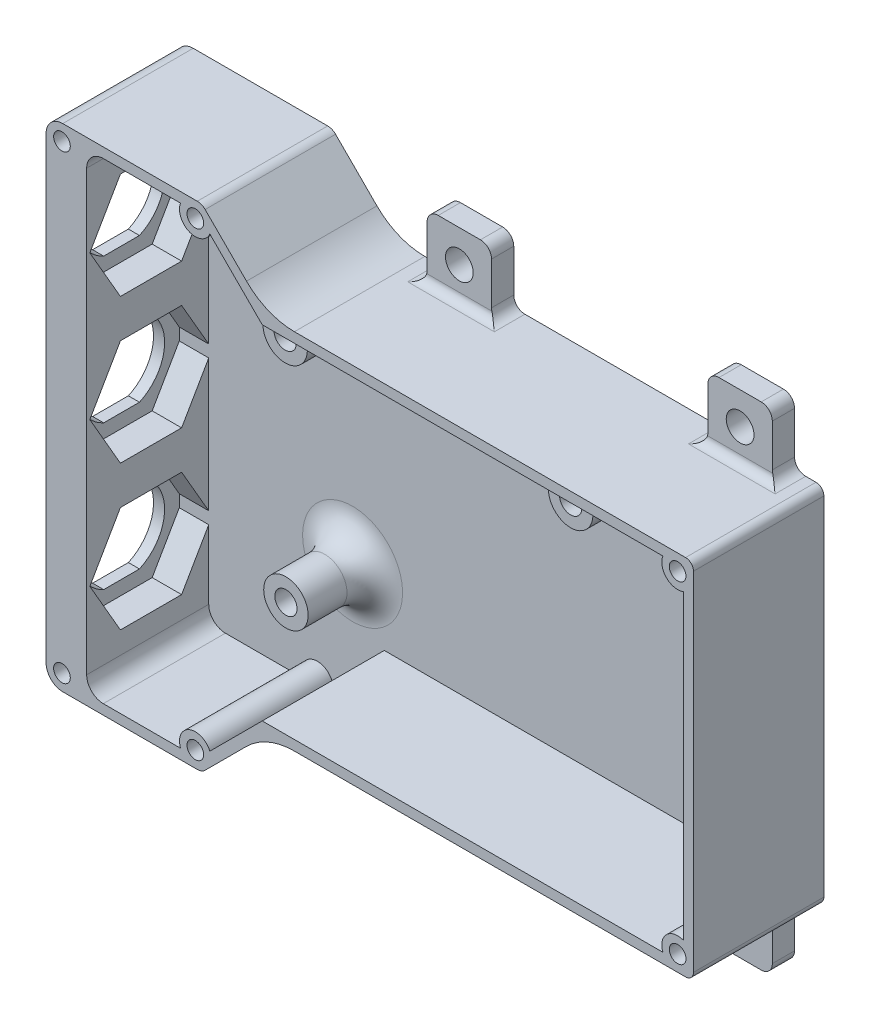
SolidWorks part; units mm, degrees
ref_plane "Front Plane" through (0, 0, 0) normal (0, 0, 1) x (1, 0, 0)
ref_plane "Top Plane" through (0, 0, 0) normal (0, 1, 0) x (1, 0, 0)
ref_plane "Right Plane" through (0, 0, 0) normal (1, 0, 0) x (0, 0, -1)
sketch "Sketch1" plane through (0, 0, 0) normal (0, 0, 1) x (1, 0, 0)
  line L0 (21.6569, -104.2696) -> (33.2669, -92.6596)
  line L1 (21.6569, -11.2696) -> (33.2619, -22.8746)
  line L2 (22.8284, -103.098) -> (34.4384, -91.488) construction
  line L3 (22.8284, -12.4412) -> (34.4334, -24.0462) construction
  line L10 (0, -100.2696) -> (20, -100.2696)
  line L11 (0, -15.2696) -> (20, -15.2696)
  line L12 (20, -100.2696) -> (31.61, -88.6596)
  line L13 (96.455, -88.6596) -> (8, -88.6596) construction
  line L14 (8, -26.8746) -> (96.455, -26.8746) construction
  line L15 (20, -15.2696) -> (31.605, -26.8746)
  line L16 (1.6569, -104.2696) -> (21.6569, -104.2696)
  line L17 (1.6569, -11.2696) -> (21.6569, -11.2696)
  line L24 (96.455, -88.6596) -> (31.61, -88.6596)
  line L26 (31.605, -26.8746) -> (96.455, -26.8746)
  line L27 (96.455, -26.8746) -> (96.455, -88.6596)
  line L28 (100.455, -92.6596) -> (33.2669, -92.6596)
  line L29 (33.2619, -22.8746) -> (100.455, -22.8746)
  line L31 (100.455, -22.8746) -> (100.455, -92.6596)
  line L33 (0, -100.2696) -> (-18.3, -100.2696)
  line L35 (0, -15.2696) -> (-18.3, -15.2696)
  line L36 (-18.3, -15.2696) -> (-18.3, -11.2696)
  line L37 (-18.3, -11.2696) -> (1.6569, -11.2696)
  line L38 (-18.3, -100.2696) -> (-18.3, -104.2696)
  line L39 (-18.3, -104.2696) -> (1.6569, -104.2696)
  line L45 (100.455, -92.6596) -> (4, -92.6596) construction
  line L46 (4, -92.6596) -> (4, -22.8746) construction
  line L47 (4, -22.8746) -> (100.455, -22.8746) construction
  line L52 (8, -88.6596) -> (8, -26.8746) construction
  dimension "D1" = 4
  dimension "D3" = 4
  dimension "D2" = 4
extrude "Boss-Extrude1" add sketch "Sketch1" along normal blind 36.78
sketch "Sketch2" plane through (0, 0, 0) normal (0, 0, -1) x (-1, 0, 0)
  line L0 (18.3, -15.2696) -> (18.3, -100.2696)
  line L16 (-33.2669, -92.6596) -> (-21.6569, -104.2696)
  line L17 (-31.61, -88.6596) -> (-96.455, -88.6596)
  line L18 (-96.455, -88.6596) -> (-96.455, -26.8746)
  line L19 (-96.455, -26.8746) -> (-31.605, -26.8746)
  line L20 (-33.2669, -92.6596) -> (-21.6569, -104.2696)
  line L21 (-20, -15.2696) -> (18.3, -15.2696)
  line L22 (18.3, -15.2696) -> (18.3, -11.2696)
  line L23 (18.3, -11.2696) -> (-21.6569, -11.2696)
  line L24 (-20, -100.2696) -> (-31.61, -88.6596)
  line L25 (-33.2619, -22.8746) -> (-100.455, -22.8746)
  line L26 (-100.455, -22.8746) -> (-100.455, -92.6596)
  line L27 (-100.455, -92.6596) -> (-33.2669, -92.6596)
  line L29 (-21.6569, -104.2696) -> (18.3, -104.2696)
  line L30 (18.3, -104.2696) -> (18.3, -100.2696)
  line L31 (18.3, -100.2696) -> (-20, -100.2696)
  line L33 (-31.605, -26.8746) -> (-20, -15.2696)
  line L35 (-21.6569, -11.2696) -> (-33.2619, -22.8746)
  line L36 (-21.6569, -11.2696) -> (-33.2619, -22.8746)
  line L38 (18.3, -15.2696) -> (18.3, -11.2696)
  line L39 (18.3, -11.2696) -> (-21.6569, -11.2696)
  line L41 (-33.2619, -22.8746) -> (-100.455, -22.8746)
  line L42 (-100.455, -22.8746) -> (-100.455, -92.6596)
  line L43 (-100.455, -92.6596) -> (-33.2669, -92.6596)
  line L45 (-21.6569, -104.2696) -> (18.3, -104.2696)
  line L46 (18.3, -104.2696) -> (18.3, -100.2696)
  dimension "D1" = 0
extrude "Boss-Extrude2" add sketch "Sketch2" against normal blind 3.5
sketch "Sketch4" plane through (-5.3, 0, 0) normal (1, 0, 0) x (0, 0, -1)
  line L0 (-13.8923, -90.5196) -> (-10.7395, -90.5196) construction
  line L1 (-13.8923, -90.5196) -> (-17.0451, -90.5196) construction
  line L2 (-13.8923, -77.0196) -> (-10.7395, -77.0196) construction
  line L3 (-13.8923, -77.0196) -> (-17.0451, -77.0196) construction
  line L4 (-13.8923, -64.5196) -> (-10.7395, -64.5196) construction
  line L5 (-13.8923, -64.5196) -> (-17.0451, -64.5196) construction
  line L6 (-13.8923, -51.0196) -> (-10.7395, -51.0196) construction
  line L7 (-13.8923, -51.0196) -> (-17.0451, -51.0196) construction
  line L8 (-13.8923, -38.5196) -> (-17.0451, -38.5196) construction
  line L9 (-13.8923, -38.5196) -> (-10.7395, -38.5196) construction
  line L10 (-13.8923, -25.0196) -> (-10.7395, -25.0196) construction
  line L11 (-13.8923, -25.0196) -> (-17.0451, -25.0196) construction
  line L12 (-13.8923, -90.5196) -> (-10.7395, -90.5196)
  line L13 (-13.8923, -90.5196) -> (-17.0451, -90.5196)
  line L14 (-13.8923, -77.0196) -> (-10.7395, -77.0196)
  line L15 (-13.8923, -77.0196) -> (-17.0451, -77.0196)
  line L16 (-13.8923, -64.5196) -> (-10.7395, -64.5196)
  line L17 (-13.8923, -64.5196) -> (-17.0451, -64.5196)
  line L18 (-13.8923, -51.0196) -> (-10.7395, -51.0196)
  line L19 (-13.8923, -51.0196) -> (-17.0451, -51.0196)
  line L20 (-13.8923, -38.5196) -> (-17.0451, -38.5196)
  line L21 (-13.8923, -38.5196) -> (-10.7395, -38.5196)
  line L22 (-13.8923, -25.0196) -> (-10.7395, -25.0196)
  line L23 (-13.8923, -25.0196) -> (-17.0451, -25.0196)
  line L24 (-13.8923, -38.8196) -> (-17.111, -38.8196)
  line L25 (-13.8923, -38.8196) -> (-10.6736, -38.8196)
  line L26 (-13.8923, -24.7196) -> (-10.6736, -24.7196)
  line L27 (-13.8923, -24.7196) -> (-17.111, -24.7196)
  line L28 (-13.8923, -64.8196) -> (-17.111, -64.8196)
  line L29 (-13.8923, -64.8196) -> (-10.6736, -64.8196)
  line L30 (-13.8923, -50.7196) -> (-10.6736, -50.7196)
  line L31 (-13.8923, -50.7196) -> (-17.111, -50.7196)
  line L32 (-13.8923, -90.8196) -> (-17.111, -90.8196)
  line L33 (-13.8923, -90.8196) -> (-10.6736, -90.8196)
  line L34 (-13.8923, -76.7196) -> (-10.6736, -76.7196)
  line L35 (-13.8923, -76.7196) -> (-17.111, -76.7196)
  line L36 (-36.78, -100.2696) -> (-3.5, -100.2696)
  line L37 (-36.78, -100.2696) -> (-3.5, -100.2696)
  line L38 (-3.5, -100.2696) -> (-3.5, -15.2696)
  line L39 (-3.5, -100.2696) -> (-3.5, -15.2696)
  line L40 (-3.5, -15.2696) -> (-36.78, -15.2696)
  line L41 (-3.5, -15.2696) -> (-36.78, -15.2696)
  line L42 (-36.78, -15.2696) -> (-36.78, -100.2696)
  arc A0 (-17.0451, -77.0196) -> (-17.0451, -90.5196) centre (-13.8923, -83.7696) ccw construction
  arc A1 (-10.7395, -90.5196) -> (-10.7395, -77.0196) centre (-13.8923, -83.7696) ccw construction
  arc A2 (-10.7395, -64.5196) -> (-10.7395, -51.0196) centre (-13.8923, -57.7696) ccw construction
  arc A3 (-17.0451, -51.0196) -> (-17.0451, -64.5196) centre (-13.8923, -57.7696) ccw construction
  arc A4 (-17.0451, -25.0196) -> (-17.0451, -38.5196) centre (-13.8923, -31.7696) ccw construction
  arc A5 (-10.7395, -38.5196) -> (-10.7395, -25.0196) centre (-13.8923, -31.7696) ccw construction
  arc A6 (-17.0451, -77.0196) -> (-17.0451, -90.5196) centre (-13.8923, -83.7696) ccw
  arc A7 (-10.7395, -90.5196) -> (-10.7395, -77.0196) centre (-13.8923, -83.7696) ccw
  arc A8 (-10.7395, -64.5196) -> (-10.7395, -51.0196) centre (-13.8923, -57.7696) ccw
  arc A9 (-17.0451, -51.0196) -> (-17.0451, -64.5196) centre (-13.8923, -57.7696) ccw
  arc A10 (-17.0451, -25.0196) -> (-17.0451, -38.5196) centre (-13.8923, -31.7696) ccw
  arc A11 (-10.7395, -38.5196) -> (-10.7395, -25.0196) centre (-13.8923, -31.7696) ccw
  arc A12 (-17.111, -24.7196) -> (-17.111, -38.8196) centre (-13.8923, -31.7696) ccw
  arc A13 (-10.6736, -38.8196) -> (-10.6736, -24.7196) centre (-13.8923, -31.7696) ccw
  arc A14 (-17.111, -50.7196) -> (-17.111, -64.8196) centre (-13.8923, -57.7696) ccw
  arc A15 (-10.6736, -64.8196) -> (-10.6736, -50.7196) centre (-13.8923, -57.7696) ccw
  arc A16 (-17.111, -76.7196) -> (-17.111, -90.8196) centre (-13.8923, -83.7696) ccw
  arc A17 (-10.6736, -90.8196) -> (-10.6736, -76.7196) centre (-13.8923, -83.7696) ccw
  line M1 (-21.5451, -64.5196) -> (-18.3923, -64.5196)
  arc M2 (-18.3923, -64.5196) -> (-18.3923, -51.0196) centre (-18.3923, -57.7696) cw
  line M3 (-18.3923, -51.0196) -> (-21.5451, -51.0196)
  arc M4 (-21.5451, -51.0196) -> (-21.5451, -64.5196) centre (-18.3923, -57.7696) ccw
  dimension "D1" = 0.3
extrude "Boss-Extrude3" add sketch "Sketch4" against normal blind 2 contours L41 L42 L37 L39 A17 L33 L32 A16 L35 L34 A15 L29 L28 A14 L31 L30 A13 L25 L24 A12 L27 L26 M1 M4 M3 M2 | M4 M1 M2 M3 region at (-5.3, -57.7696, 35.8672) region at (-5.3, -57.7696, 25.6881)
sketch "Sketch5" plane through (-5.3, 0, 0) normal (1, 0, 0) x (0, 0, -1)
  line L18 (-13.8923, -24.7196) -> (-13.8923, -38.8196)
  line L19 (-10.6736, -24.7196) -> (-17.111, -24.7196) construction
  line L20 (-17.111, -38.8196) -> (-10.6736, -38.8196) construction
  line L21 (-13.8923, -50.7196) -> (-13.8923, -64.8196)
  line L22 (-10.6736, -50.7196) -> (-17.111, -50.7196) construction
  line L23 (-17.111, -64.8196) -> (-10.6736, -64.8196) construction
  line L24 (-13.8923, -76.7196) -> (-13.8923, -90.8196)
  line L25 (-10.6736, -76.7196) -> (-17.111, -76.7196) construction
  line L26 (-17.111, -90.8196) -> (-10.6736, -90.8196) construction
  line L27 (-24.9116, -83.7696) -> (-19.402, -93.3126)
  line L28 (-24.7384, -31.7696) -> (-19.3154, -41.1626)
  line L29 (-19.3154, -41.1626) -> (-8.4692, -41.1626)
  line L30 (-8.4692, -41.1626) -> (-3.0462, -31.7696)
  line L31 (-3.0462, -31.7696) -> (-8.4692, -22.3766)
  line L32 (-8.4692, -22.3766) -> (-19.3154, -22.3766)
  line L33 (-19.3154, -22.3766) -> (-24.7384, -31.7696)
  line L34 (-24.7384, -57.7696) -> (-19.3154, -67.1626)
  line L35 (-19.3154, -67.1626) -> (-8.4692, -67.1626)
  line L36 (-36.78, -100.2696) -> (-3.5, -100.2696) construction
  line L37 (-36.78, -15.2696) -> (-36.78, -100.2696) construction
  line L38 (-3.5, -15.2696) -> (-36.78, -15.2696) construction
  line L39 (-3.5, -100.2696) -> (-3.5, -15.2696) construction
  line L40 (-36.78, -100.2696) -> (-3.5, -100.2696)
  line L41 (-36.78, -15.2696) -> (-36.78, -100.2696)
  line L42 (-3.5, -15.2696) -> (-36.78, -15.2696)
  line L43 (-3.5, -100.2696) -> (-3.5, -15.2696)
  line L44 (-8.4692, -67.1626) -> (-3.0462, -57.7696)
  line L45 (-3.0462, -57.7696) -> (-8.4692, -48.3766)
  line L46 (-8.4692, -48.3766) -> (-19.3154, -48.3766)
  line L47 (-19.3154, -48.3766) -> (-24.7384, -57.7696)
  line L48 (-24.7384, -83.7696) -> (-19.3154, -93.1626)
  line L49 (-19.3154, -93.1626) -> (-8.4692, -93.1626)
  line L50 (-8.4692, -93.1626) -> (-3.0462, -83.7696)
  line L51 (-3.0462, -83.7696) -> (-8.4692, -74.3766)
  line L52 (-8.4692, -74.3766) -> (-19.3154, -74.3766)
  line L53 (-19.3154, -74.3766) -> (-24.7384, -83.7696)
  line L54 (-19.402, -93.3126) -> (-8.3826, -93.3126)
  line L55 (-8.3826, -93.3126) -> (-2.873, -83.7696)
  line L56 (-2.873, -83.7696) -> (-8.3826, -74.2266)
  line L57 (-8.3826, -74.2266) -> (-19.402, -74.2266)
  line L58 (-19.402, -74.2266) -> (-24.9116, -83.7696)
  line L59 (-19.402, -22.2266) -> (-24.9116, -31.7696)
  line L60 (-24.9116, -31.7696) -> (-19.402, -41.3126)
  line L61 (-19.402, -41.3126) -> (-8.3826, -41.3126)
  line L62 (-8.3826, -41.3126) -> (-2.873, -31.7696)
  line L63 (-2.873, -31.7696) -> (-8.3826, -22.2266)
  line L64 (-8.3826, -22.2266) -> (-19.402, -22.2266)
  line L65 (-19.402, -48.2266) -> (-24.9116, -57.7696)
  line L66 (-24.9116, -57.7696) -> (-19.402, -67.3126)
  line L67 (-19.402, -67.3126) -> (-8.3826, -67.3126)
  line L68 (-8.3826, -67.3126) -> (-2.873, -57.7696)
  line L69 (-2.873, -57.7696) -> (-8.3826, -48.2266)
  line L70 (-8.3826, -48.2266) -> (-19.402, -48.2266)
  circle A0 centre (-13.8923, -31.7696) radius 9.393 construction
  circle A1 centre (-13.8923, -57.7696) radius 9.393 construction
  circle A2 centre (-13.8923, -83.7696) radius 9.393 construction
  line M16 (-3.5, -15.2696) -> (-36.78, -15.2696)
  line M17 (-36.78, -15.2696) -> (-36.78, -100.2696)
  line M18 (-36.78, -100.2696) -> (-3.5, -100.2696)
  line M19 (-3.5, -100.2696) -> (-3.5, -15.2696)
  dimension "D1" = 0.15
extrude "Boss-Extrude4" add sketch "Sketch5" along normal up to surface (5.3 mm away) contours L46 L45 L44 L34 L32 L30 L29 L28 M19 M16 M17 M18 region at (-5.3, -88.9975, 22.9473)
sketch "Sketch6" plane through (0, 0, 36.78) normal (0, 0, 1) x (1, 0, 0)
  line L1 (-48.9743, 0) -> (133.8378, 0)
  line L2 (-48.9743, 0) -> (-48.9743, -122.4446)
  line L3 (-48.9743, -122.4446) -> (133.8378, -122.4446)
  line L4 (133.8378, 0) -> (133.8378, -122.4446)
extrude "Cut-Extrude1" cut sketch "Sketch6" against normal blind 4
ref_plane "Plane1" through (5, 0, 0) normal (1, 0, 0) x (0, 0, -1)
fillet "Fillet4" radius 10 2 edges at (33.2669, -92.6596, 16.39) (33.2619, -22.8746, 16.39)
sketch "Sketch8" plane through (0, 0, 32.78) normal (0, 0, 1) x (1, 0, 0)
  line L0 (100.455, -92.6596) -> (100.455, -22.8746) construction
  line L3 (100.455, -88.6596) -> (100.455, -26.8746)
  line L6 (96.455, -26.8746) -> (96.455, -88.6596)
  line L7 (96.455, -26.8746) -> (100.455, -26.8746)
  line L8 (96.455, -88.6596) -> (100.455, -88.6596)
extrude "Cut-Extrude2" cut sketch "Sketch8" against normal up to surface (29.28 mm away) up to face at (13.2163, -57.7691, 3.5)
sketch "Sketch9" plane through (100.455, 0, 0) normal (1, 0, 0) x (0, 0, -1)
  line L0 (-32.78, -92.6596) -> (-32.78, -88.6596) construction
  line L1 (-3.5, -88.6596) -> (-32.78, -88.6596) construction
  line L2 (-32.78, -92.6596) -> (0, -92.6596) construction
  line L3 (0, -92.6596) -> (0, -22.8746) construction
  line L4 (-3.5, -88.6596) -> (-3.5, -26.8746) construction
  line L5 (-3.5, -26.8746) -> (-32.78, -26.8746) construction
  line L6 (-32.78, -26.8746) -> (-32.78, -22.8746) construction
  line L7 (-32.78, -22.8746) -> (0, -22.8746) construction
  line L8 (-32.78, -92.6596) -> (-32.78, -88.6596)
  line L9 (-3.5, -88.6596) -> (-32.78, -88.6596)
  line L10 (-32.78, -92.6596) -> (0, -92.6596)
  line L11 (0, -92.6596) -> (0, -22.8746)
  line L12 (-3.5, -88.6596) -> (-3.5, -26.8746)
  line L13 (-3.5, -26.8746) -> (-32.78, -26.8746)
  line L14 (-32.78, -26.8746) -> (-32.78, -22.8746)
  line L15 (-32.78, -22.8746) -> (0, -22.8746)
extrude "Boss-Extrude6" add sketch "Sketch9" along normal blind 11
sketch "Sketch10" plane through (0, 0, 32.78) normal (0, 0, 1) x (1, 0, 0)
  line L0 (111.455, -88.6596) -> (31.61, -88.6596) construction
  line L2 (31.605, -26.8746) -> (111.455, -26.8746) construction
  line L4 (111.455, -88.6596) -> (107.455, -88.6596)
  line L6 (107.455, -26.8746) -> (111.455, -26.8746)
  line L8 (111.455, -26.8746) -> (107.455, -26.8746)
  line L9 (107.455, -26.8746) -> (107.455, -88.6596)
  line L10 (111.455, -26.8746) -> (111.455, -88.6596)
  line M1 (31.605, -26.8746) -> (111.455, -26.8746)
  line M19 (111.455, -88.6596) -> (31.61, -88.6596)
extrude "Boss-Extrude7" add sketch "Sketch10" against normal up to surface (29.28 mm away) contours L10 L9 M1 M19 region at (109.455, -57.7671, 32.78) up to face at (-12.8, -57.7696, 3.5)
sketch "Sketch24" plane through (0, 0, 32.78) normal (0, 0, 1) x (1, 0, 0)
  line L2 (111.455, -22.8746) -> (37.404, -22.8746) construction
  line L3 (111.455, -22.8746) -> (111.455, -92.6596) construction
  line L4 (31.605, -26.8746) -> (107.455, -26.8746) construction
  line L5 (107.455, -26.8746) -> (107.455, -88.6596) construction
  line L6 (111.455, -22.8746) -> (37.404, -22.8746)
  line L7 (111.455, -22.8746) -> (111.455, -92.6596)
  line L8 (31.605, -26.8746) -> (107.455, -26.8746)
  line L9 (107.455, -26.8746) -> (107.455, -88.6596)
  line L10 (107.455, -26.8746) -> (107.455, -29.8746)
  line L11 (107.455, -26.8746) -> (104.455, -26.8746)
  line L12 (104.455, -26.8746) -> (107.455, -29.8746)
  line L13 (107.455, -88.6596) -> (104.455, -88.6596)
  line L14 (107.455, -88.6596) -> (31.61, -88.6596) construction
  line L15 (104.455, -88.6596) -> (107.455, -85.6596)
  line M1 (107.455, -26.8746) -> (107.455, -88.6596)
  line M2 (107.455, -88.6596) -> (31.61, -88.6596)
extrude "Boss-Extrude10" add sketch "Sketch24" against normal up to surface (29.28 mm away) contours L15 M2 M1 | L8 L12 M1 region at (106.455, -87.6596, 32.78) region at (106.455, -27.8746, 32.78) up to face at (-12.8, -57.7696, 3.5)
sketch "Sketch28" plane through (0, 0, 32.78) normal (0, 0, 1) x (1, 0, 0)
  line L1 (-7.3, -83.7696) -> (-7.3, -31.7696)
  line L2 (-7.3, -31.7696) -> (-7.3, -6.2489)
  line L3 (-7.3, -6.2489) -> (-26.3455, -6.2489)
  line L4 (-26.3455, -6.2489) -> (-26.3455, -107.7031)
  line L5 (-26.3455, -107.7031) -> (-7.3, -107.7031)
  line L6 (-7.3, -107.7031) -> (-7.3, -83.7696)
extrude "Cut-Extrude12" cut sketch "Sketch28" against normal through all
sketch "Sketch29" plane through (0, 0, 32.78) normal (0, 0, 1) x (1, 0, 0)
  line L0 (-7.3, -104.2696) -> (21.6569, -104.2696) construction
  line L1 (21.6569, -104.2696) -> (30.3379, -95.5885) construction
  line L2 (37.409, -92.6596) -> (111.455, -92.6596) construction
  line L3 (111.455, -22.8746) -> (111.455, -92.6596) construction
  line L4 (111.455, -22.8746) -> (37.404, -22.8746) construction
  line L5 (30.3329, -19.9457) -> (21.6569, -11.2696) construction
  line L6 (21.6569, -11.2696) -> (-7.3, -11.2696) construction
  line L7 (-7.3, -104.2696) -> (21.6569, -104.2696)
  line L8 (21.6569, -104.2696) -> (30.3379, -95.5885)
  line L9 (37.409, -92.6596) -> (111.455, -92.6596)
  line L10 (111.455, -22.8746) -> (111.455, -92.6596)
  line L11 (111.455, -22.8746) -> (37.404, -22.8746)
  line L12 (30.3329, -19.9457) -> (21.6569, -11.2696)
  line L13 (21.6569, -11.2696) -> (-7.3, -11.2696)
  line L14 (-7.3, -102.0736) -> (20.7472, -102.0736)
  line L15 (20.7472, -102.0736) -> (28.7851, -94.0357)
  line L16 (37.409, -90.4636) -> (109.259, -90.4636)
  line L17 (109.259, -25.0706) -> (109.259, -90.4636)
  line L18 (109.259, -25.0706) -> (37.404, -25.0706)
  line L19 (28.7801, -21.4985) -> (20.7472, -13.4656)
  line L20 (20.7472, -13.4656) -> (-7.3, -13.4656)
  line L21 (-7.3, -13.4656) -> (-7.3, -11.2696)
  line L22 (-7.3, -102.0736) -> (-7.3, -104.2696)
  arc A0 (37.409, -92.6596) -> (30.3379, -95.5885) centre (37.409, -102.6596) ccw construction
  arc A1 (30.3329, -19.9457) -> (37.404, -22.8746) centre (37.404, -12.8746) ccw construction
  arc A2 (37.409, -92.6596) -> (30.3379, -95.5885) centre (37.409, -102.6596) ccw
  arc A3 (30.3329, -19.9457) -> (37.404, -22.8746) centre (37.404, -12.8746) ccw
  arc A4 (37.409, -90.4636) -> (28.7851, -94.0357) centre (37.409, -102.6596) ccw
  arc A5 (28.7801, -21.4985) -> (37.404, -25.0706) centre (37.404, -12.8746) ccw
  dimension "D1" = 2.196
extrude "Cut-Extrude13" cut sketch "Sketch29" against normal through all
sketch "Sketch30" plane through (0, 0, 0) normal (0, 0, -1) x (-1, 0, 0)
  line L0 (-37.404, -25.0706) -> (-109.259, -25.0706) construction
  line L1 (-109.259, -25.0706) -> (-109.259, -90.4636) construction
  line L2 (-109.259, -90.4636) -> (-37.409, -90.4636) construction
  line L3 (-28.7851, -94.0357) -> (-20.7472, -102.0736) construction
  line L4 (-20.7472, -102.0736) -> (7.3, -102.0736) construction
  line L5 (7.3, -102.0736) -> (7.3, -13.4656) construction
  line L6 (7.3, -13.4656) -> (-20.7472, -13.4656) construction
  line L7 (-20.7472, -13.4656) -> (-28.7801, -21.4985) construction
  line L8 (-109.259, -25.0706) -> (-109.259, -90.4636)
  line L9 (-109.259, -90.4636) -> (-37.409, -90.4636)
  line L10 (-28.7851, -94.0357) -> (-20.7472, -102.0736)
  line L11 (-20.7472, -102.0736) -> (7.3, -102.0736)
  line L12 (7.3, -102.0736) -> (7.3, -13.4656)
  line L13 (7.3, -13.4656) -> (-20.7472, -13.4656)
  line L14 (-20.7472, -13.4656) -> (-28.7801, -21.4985)
  line L15 (-37.404, -25.0706) -> (-109.259, -25.0706)
  arc A0 (-28.7851, -94.0357) -> (-37.409, -90.4636) centre (-37.409, -102.6596) ccw construction
  arc A1 (-37.404, -25.0706) -> (-28.7801, -21.4985) centre (-37.404, -12.8746) ccw construction
  arc A2 (-28.7851, -94.0357) -> (-37.409, -90.4636) centre (-37.409, -102.6596) ccw
  arc A3 (-37.404, -25.0706) -> (-28.7801, -21.4985) centre (-37.404, -12.8746) ccw
extrude "Cut-Extrude14" cut sketch "Sketch30" against normal blind 2
fillet "Fillet26" radius 3 2 edges at (-7.3, -13.4656, 17.39) (-7.3, -102.0736, 17.39)
fillet "Fillet27" radius 3 2 edges at (0, -100.2696, 18.14) (0, -15.2696, 18.14)
fillet "Fillet28" radius 2 4 edges at (20, -15.2696, 18.14) (20.7472, -13.4656, 17.39) (20, -100.2696, 18.14) (20.7472, -102.0736, 17.39) tangent propagation no
sketch "Sketch33" plane through (0, 0, 32.78) normal (0, 0, 1) x (1, 0, 0)
  line L2 (109.259, -25.0706) -> (109.259, -90.4636) construction
  line L3 (109.259, -90.4636) -> (37.409, -90.4636) construction
  line L4 (19.9188, -102.0736) -> (-4.3, -102.0736) construction
  line L5 (28.7851, -94.0357) -> (21.333, -101.4878) construction
  line L6 (-4.3, -13.4656) -> (19.9188, -13.4656) construction
  line L7 (21.333, -14.0514) -> (28.7801, -21.4985) construction
  line L8 (-7.3, -99.0736) -> (-7.3, -16.4656) construction
  line L9 (37.404, -25.0706) -> (109.259, -25.0706) construction
  circle A0 centre (106.406, -27.9236) radius 1.5
  circle A1 centre (106.406, -27.9236) radius 2.853
  circle A2 centre (106.406, -87.6106) radius 2.853
  circle A3 centre (19.5655, -99.2206) radius 2.853
  circle A4 centre (19.5655, -16.3186) radius 2.853
  circle A5 centre (-4.447, -16.3186) radius 2.853
  circle A6 centre (-4.447, -99.2206) radius 2.853
  dimension "D3" = 3
  dimension "D4" = 5.706
  dimension "D2" = 2.853
extrude "Boss-Extrude13" add sketch "Sketch33" against normal up to surface (29.28 mm away) contours A4 | A3 | A2 | A1 up to face at (20.7548, -57.769, 3.5)
sketch "Sketch34" plane through (0, 0, 32.78) normal (0, 0, 1) x (1, 0, 0)
  circle A0 centre (106.406, -27.9236) radius 2.853 construction
  circle A1 centre (106.406, -87.6106) radius 2.853 construction
  circle A2 centre (19.5655, -99.2206) radius 2.853 construction
  circle A3 centre (-4.447, -99.2206) radius 2.853 construction
  circle A4 centre (19.5655, -16.3186) radius 2.853 construction
  circle A5 centre (-4.447, -16.3186) radius 2.853 construction
  circle A6 centre (106.406, -27.9236) radius 2.853
  circle A7 centre (106.406, -87.6106) radius 2.853
  circle A8 centre (19.5655, -99.2206) radius 2.853
  circle A9 centre (-4.447, -99.2206) radius 2.853
  circle A10 centre (19.5655, -16.3186) radius 2.853
  circle A11 centre (-4.447, -16.3186) radius 2.853
  circle A12 centre (-4.447, -16.3186) radius 1.5
  circle A13 centre (19.5655, -16.3186) radius 1.5
  circle A14 centre (106.406, -27.9236) radius 1.5
  circle A15 centre (106.406, -87.6106) radius 1.5
  circle A16 centre (19.5655, -99.2206) radius 1.5
  circle A17 centre (-4.447, -99.2206) radius 1.5
extrude "Cut-Extrude15" cut sketch "Sketch34" against normal blind 20 contours A12 | A13 | A14 | A15 | A16 | A17
fillet "Fillet29" radius 1.425 2 edges at (109.259, -25.0706, 17.39) (109.259, -90.4636, 17.39)
ref_plane "Plane2" through (0, 0, 20.78) normal (0, 0, 1) x (1, 0, 0)
sketch "Sketch35" plane through (0, 0, 20.78) normal (0, 0, 1) x (1, 0, 0)
  line L0 (31.61, -88.6596) -> (103.7528, -88.6596) construction
  line L1 (107.455, -30.5767) -> (107.455, -84.9574) construction
  line L2 (103.7528, -26.8746) -> (31.605, -26.8746) construction
  line L3 (31.61, -88.6596) -> (103.7528, -88.6596)
  line L4 (107.455, -30.5767) -> (107.455, -84.9574)
  line L5 (103.7528, -26.8746) -> (31.605, -26.8746)
  line L6 (107.455, -84.9574) -> (107.455, -88.6596)
  line L7 (107.455, -88.6596) -> (103.7528, -88.6596)
  line L8 (103.7528, -26.8746) -> (107.455, -26.8746)
  line L9 (107.455, -26.8746) -> (107.455, -30.5767)
  line L10 (31.605, -26.8746) -> (31.61, -88.6596)
extrude "Cut-Extrude16" cut sketch "Sketch35" against normal up to surface (17.28 mm away) up to face at (20.4692, -57.769, 3.5)
sketch "Sketch36" plane through (0, 0, 32.78) normal (0, 0, 1) x (1, 0, 0)
  line L1 (-22.7026, -2.6518) -> (121.9699, -2.6518)
  line L2 (-22.7026, -2.6518) -> (-22.7026, -112.3259)
  line L3 (-22.7026, -112.3259) -> (121.9699, -112.3259)
  line L4 (121.9699, -2.6518) -> (121.9699, -112.3259)
extrude "Cut-Extrude17" cut sketch "Sketch36" against normal blind 7.3
sketch "Sketch38" plane through (0, 0, 3.5) normal (0, 0, 1) x (1, 0, 0)
  circle A2 centre (25.7592, -36.7486) radius 2
  circle A4 centre (77.1688, -36.7486) radius 2
  circle A6 centre (25.8989, -78.0236) radius 2
  circle A7 centre (102.7085, -78.0236) radius 4
  circle A8 centre (102.7085, -78.0236) radius 2
  circle A9 centre (77.1688, -36.7486) radius 4
  circle A10 centre (25.7592, -36.7486) radius 4
  circle A11 centre (25.8989, -78.0236) radius 4
  dimension "D1" = 2
extrude "Boss-Extrude14" add sketch "Sketch38" along normal up to surface (12 mm away) contours A7 A8 | A11 A6 | A10 A2 | A9 A4 region at (98.8216, -78.0236, 3.5) region at (73.2819, -36.7486, 3.5) region at (21.8723, -36.7486, 3.5) region at (22.012, -78.0236, 3.5)
fillet "Fillet30" radius 5 4 edges at (98.7085, -78.0236, 3.5) (73.1688, -36.7486, 3.5) (21.7592, -36.7486, 3.5) (21.8989, -78.0236, 3.5)
sketch "Sketch39" plane through (0, 0, 2) normal (0, 0, -1) x (-1, 0, 0)
  line L0 (-107.834, -90.4636) -> (-37.409, -90.4636) construction
  line L1 (-37.404, -25.0706) -> (-107.834, -25.0706) construction
  line L2 (-107.834, -90.4636) -> (-37.409, -90.4636)
  line L3 (-37.404, -25.0706) -> (-107.834, -25.0706)
  line L4 (-103.9747, -25.0706) -> (-103.9747, -13.4706)
  line L5 (-103.9747, -13.4706) -> (-92.3747, -13.4706)
  line L6 (-92.3747, -13.4706) -> (-92.3747, -25.0706)
  line L7 (-53.4219, -25.0706) -> (-53.4219, -13.4706)
  line L8 (-53.4219, -13.4706) -> (-41.8219, -13.4706)
  line L9 (-41.8219, -13.4706) -> (-41.8219, -25.0706)
  line L10 (-109.259, -57.7671) -> (-21.9967, -57.7671)
  line L11 (-109.259, -26.4956) -> (-109.259, -89.0386) construction
  line L12 (-37.404, -90.4636) -> (-107.834, -90.4636)
  line L13 (-41.8219, -102.0636) -> (-41.8219, -90.4636)
  line L14 (-53.4219, -102.0636) -> (-41.8219, -102.0636)
  line L15 (-53.4219, -90.4636) -> (-53.4219, -102.0636)
  line L16 (-103.9747, -90.4636) -> (-103.9747, -102.0636)
  line L17 (-103.9747, -102.0636) -> (-92.3747, -102.0636)
  line L18 (-92.3747, -102.0636) -> (-92.3747, -90.4636)
  line L19 (4.3, -13.4656) -> (-19.9188, -13.4656) construction
  line L20 (-19.9188, -102.0736) -> (4.3, -102.0736) construction
  line L21 (4.3, -13.4656) -> (-19.9188, -13.4656)
  line L22 (-19.9188, -102.0736) -> (4.3, -102.0736)
  circle A0 centre (-98.1747, -19.2706) radius 2.5
  circle A1 centre (-47.6219, -19.2706) radius 2.5
  circle A2 centre (-47.6219, -96.2636) radius 2.5
  circle A3 centre (-98.1747, -96.2636) radius 2.5
  point P39 (-103.9747, -96.2636)
  point P41 (-98.1747, -102.0636)
  point P42 (-53.4219, -96.2636)
  point P43 (-47.6219, -102.0636)
  dimension "D1" = 11.6
  dimension "D2" = 11.6
  dimension "D3" = 11.6
  dimension "D4" = 11.6
extrude "Boss-Extrude15" add sketch "Sketch39" against normal blind 4 contours L9 L8 L7 L3 A1 | L6 L5 L4 L3 A0 | L17 L18 L12 L16 A3 | L12 L15 L14 L13 A2 region at (47.6219, -90.6276, 2) region at (98.1747, -90.6276, 2) region at (98.1747, -24.9066, 2) region at (47.6219, -24.9066, 2)
fillet "Fillet31" radius 2 16 edges at (53.4219, -102.0636, 4) (53.4219, -90.4636, 4) (41.8219, -90.4636, 4) (41.8219, -102.0636, 4) (92.3747, -90.4636, 4) (92.3747, -102.0636, 4) (103.9747, -102.0636, 4) (103.9747, -90.4636, 4) (103.9747, -25.0706, 4) (103.9747, -13.4706, 4) (92.3747, -13.4706, 4) (92.3747, -25.0706, 4) (41.8219, -25.0706, 4) (53.4219, -25.0706, 4) (41.8219, -13.4706, 4) (53.4219, -13.4706, 4)
fillet "Fillet32" radius 1.5 4 edges at (47.6219, -25.0706, 6) (98.1747, -25.0706, 6) (98.1747, -90.4636, 6) (47.6219, -90.4636, 6)
